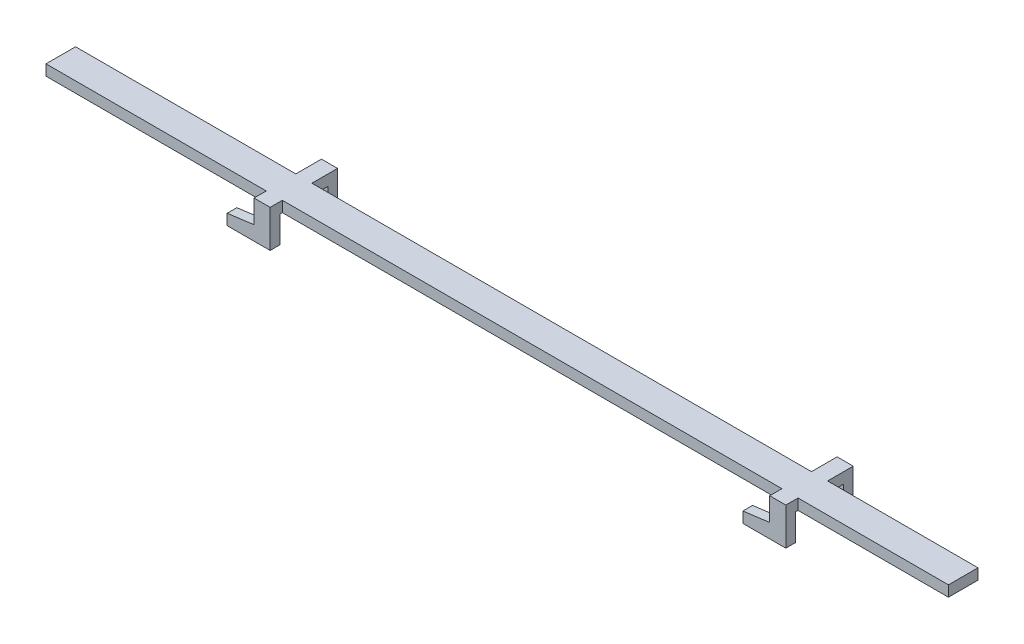
SolidWorks part; units mm, degrees
ref_plane "Top" through (0, 0, 0) normal (0, 0, 1) x (1, 0, 0)
ref_plane "Front" through (0, 0, 0) normal (0, 1, 0) x (1, 0, 0)
ref_plane "Right" through (0, 0, 0) normal (1, 0, 0) x (0, 0, -1)
sketch "Top Sketch" plane through (0, 0, 0) normal (0, 1, 0) x (1, 0, 0)
  line L0 (-28, -5.5) -> (-28, -6.875)
  line L1 (-168, 0) -> (-127, 0)
  line L2 (-168, 0) -> (-168, -5.5)
  line L3 (-168, -5.5) -> (-127, -5.5)
  line L4 (0, 0) -> (0, -5.5)
  line L5 (-28, -6.875) -> (-36, -6.875) construction
  line L6 (-36, -6.875) -> (-36, -5.5) construction
  line L7 (-124, -5.5) -> (-124, -6.875)
  line L8 (-124, -6.875) -> (-132, -6.875) construction
  line L9 (-132, -6.875) -> (-132, -5.5) construction
  line L10 (-28, 0) -> (-28, 3.875)
  line L11 (-28, 3.875) -> (-36, 3.875) construction
  line L12 (-36, 3.875) -> (-36, 0) construction
  line L13 (-124, 0) -> (-124, 3.875)
  line L14 (-124, 3.875) -> (-132, 3.875) construction
  line L15 (-132, 3.875) -> (-132, 0) construction
  line L16 (-28, 0) -> (0, 0)
  line L17 (-28, -5.5) -> (0, -5.5)
  line L18 (-124, 0) -> (-31, 0)
  line L19 (-124, -5.5) -> (-31, -5.5)
  line L20 (-31, 3.875) -> (-31, 0)
  line L21 (-31, 3.875) -> (-28, 3.875)
  line L22 (-31, -5.5) -> (-31, -6.875)
  line L23 (-31, -6.875) -> (-28, -6.875)
  line L24 (-127, 3.875) -> (-127, 0)
  line L25 (-127, 3.875) -> (-124, 3.875)
  line L26 (-127, -6.875) -> (-127, -5.5)
  line L27 (-127, -6.875) -> (-124, -6.875)
  line L28 (-168, -15.863) -> (0, -15.863) construction
  point P32 (-84, -15.863)
  dimension "D1" = 5.5
  dimension "Length" = 168
  dimension "D3" = 1.375
  dimension "D5" = 5
  dimension "D6" = 3.875
  dimension "D8" = 3
extrude "Thickness Extrude" add sketch "Top Sketch" along normal blind 2
sketch "Hook Sketch" plane through (0, 0, 6.875) normal (0, 0, 1) x (1, 0, 0)
  line L0 (-31, 2) -> (-28, 2)
  line L1 (-31, 0) -> (-28, 0) construction
  line L2 (-28, 2) -> (-28, -4.9583)
  line L3 (-28, -4.9583) -> (-36, -4.9583)
  line L4 (-36, -4.9583) -> (-36, -2.9583)
  line L5 (-36, -2.9583) -> (-31, -2.3)
  line L6 (-31, -2.3) -> (-31, 2)
  dimension "D1" = 7.5
  dimension "D2" = 5
  dimension "D3" = 2.3
  dimension "D4" = 2
extrude "Hook 1 Extrude" add sketch "Hook Sketch" against normal blind 0.9 and the other way blind 0.9 separate body
extrude "Hook 2 Extrude" add sketch "Hook Sketch<2>" along normal blind 0.9 and the other way blind 0.9 from surface separate body starting at face at (-29.5, 1, -3.875)
sketch "Hook Sketch<2>" plane through (0, 0, 6.875) normal (0, 0, 1) x (1, 0, 0) same geometry as "Hook Sketch"
pattern_linear "Hook Pattern" count 2 spacing 96 along (-1, 0, 0) of "Hook 1 Extrude", "Hook 2 Extrude"
combine bodies "Combine Bodies" operation type add bodies to combine 101 103 104 105 106
